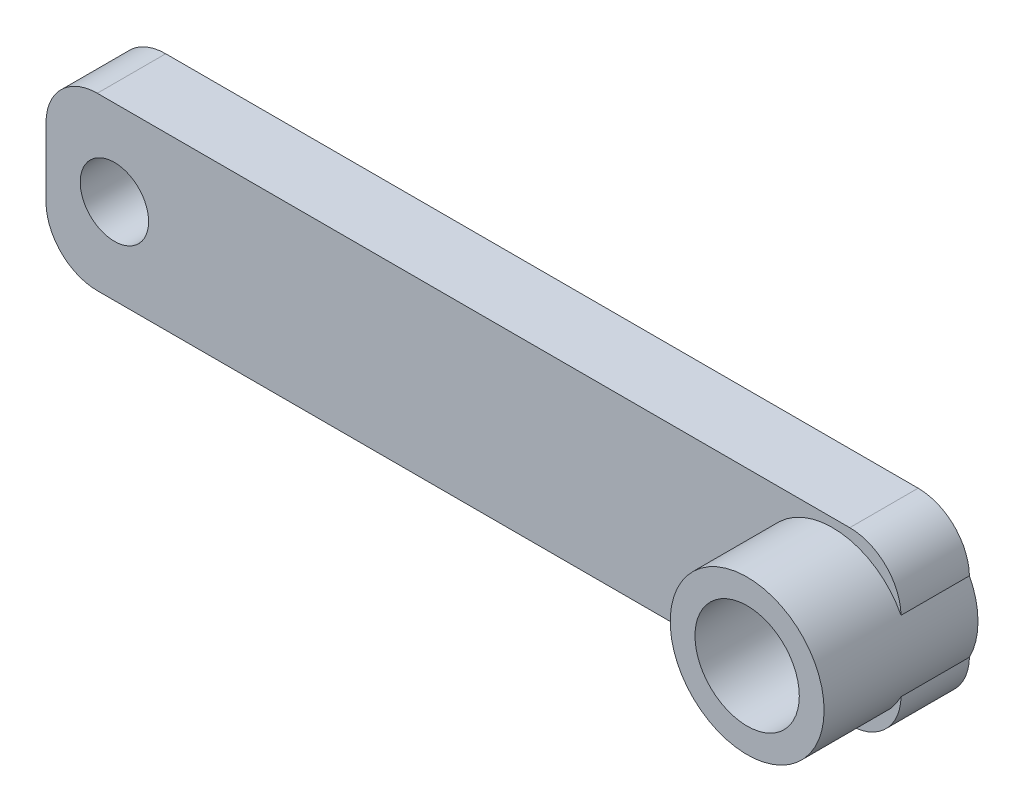
SolidWorks part; units mm, degrees
ref_plane "前视基准面" through (0, 0, 0) normal (0, 0, 1) x (1, 0, 0)
ref_plane "上视基准面" through (0, 0, 0) normal (0, 1, 0) x (1, 0, 0)
ref_plane "右视基准面" through (0, 0, 0) normal (1, 0, 0) x (0, 0, -1)
sketch "草图1" plane through (0, 0, 0) normal (0, 0, 1) x (1, 0, 0)
  line L0 (0, 5) -> (0, -5) construction
  line L1 (-25, 5) -> (25, 5)
  line L2 (-25, 5) -> (-25, -5)
  line L3 (-25, -5) -> (25, -5)
  line L4 (25, 5) -> (25, -5)
  line L5 (-25, 5) -> (25, -5) construction
  line L6 (-25, -5) -> (25, 5) construction
  circle A1 centre (21, 0) radius 3.05
  circle A2 centre (-21, 0) radius 2
  point P0 (0, 0)
  dimension "D3" = 4
  dimension "D4" = 4
  dimension "D5" = 4
  dimension "D6" = 6.1
  dimension "D1" = 50
  dimension "D2" = 10
extrude "凸台-拉伸1" add sketch "草图1" along normal blind 4
sketch "草图2" plane through (0, 0, 4) normal (0, 0, 1) x (1, 0, 0)
  circle A0 centre (21, 0) radius 4.5
  circle A1 centre (21, 0) radius 3.05
  circle A2 centre (21, 0) radius 3.05
  dimension "D2" = 9
  dimension "D1" = 0
extrude "凸台-拉伸2" add sketch "草图2" along normal blind 5 and the other way blind 4
fillet "圆角1" radius 3 4 edges at (25, -5, 2) (25, 5, 2) (-25, -5, 2) (-25, 5, 2)
